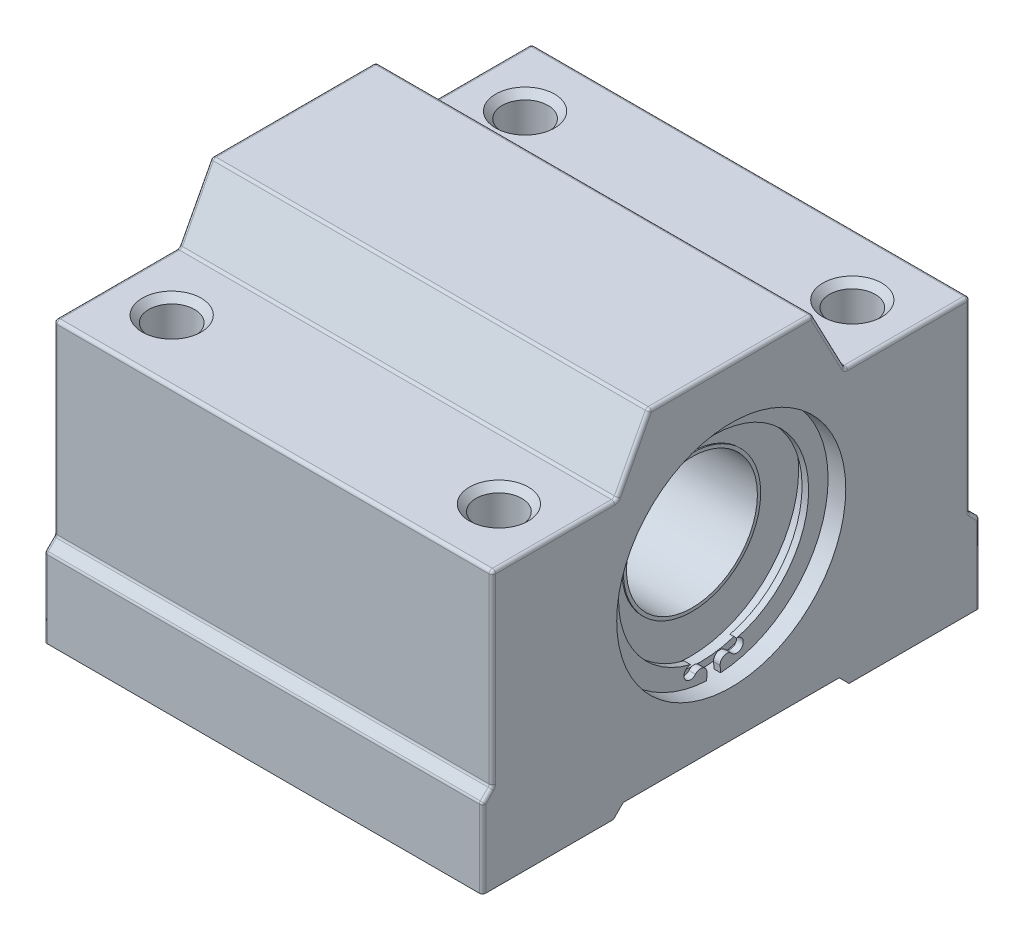
SolidWorks part; units mm, degrees
ref_plane "Front Plane" through (0, 0, 0) normal (0, 0, 1) x (1, 0, 0)
ref_plane "Top Plane" through (0, 0, 0) normal (0, 1, 0) x (1, 0, 0)
ref_plane "Right Plane" through (0, 0, 0) normal (1, 0, 0) x (0, 0, -1)
sketch "Sketch1" plane through (0, 0, 0) normal (1, 0, 0) x (0, 0, -1)
  line L1 (-18, -26) -> (-16.5, -24.5)
  line L2 (-16.5, -24.5) -> (16.5, -24.5)
  line L3 (16.5, -24.5) -> (18, -26)
  line L4 (18, -26) -> (38, -26)
  line L6 (38, -14) -> (36.5, -12.5)
  line L8 (36.5, 16) -> (17.5, 16)
  line L9 (17.5, 16) -> (12.5, 25.5)
  line L10 (12.5, 25.5) -> (-12.5, 25.5)
  line L11 (-12.5, 25.5) -> (-17.5, 16)
  line L12 (-17.5, 16) -> (-36.5, 16)
  line L15 (-38, -14) -> (-38, -26)
  line L16 (0, -24.5) -> (0, 25.5) construction
  line L17 (-16.278, 0) -> (14.0247, 0) construction
  line L18 (-38, -26) -> (-18, -26)
  line L19 (38, -14) -> (38, -26)
  line L20 (-36.5, -12.5) -> (-36.5, 16)
  line L21 (36.5, -12.5) -> (36.5, 16)
  line L22 (-27, 16) -> (-27, -26) construction
  line L23 (-27, -26) -> (27, 16) construction
  line L24 (27, 16) -> (27, -26) construction
  line L25 (-38, -14) -> (-36.5, -12.5)
  line L26 (-17.5, 0) -> (17.5, 0) construction
  circle A0 centre (0, 0) radius 17.5
  circle A1 centre (0, 0) radius 16.5
  circle A2 centre (0, 0) radius 10
  point P18 (0, 25.5)
  point P23 (0, 0)
  dimension "D12" = 20
  dimension "D1" = 76
  dimension "D2" = 42
  dimension "D3" = 26
  dimension "D5" = 51.5
  dimension "D6" = 54
  dimension "D4" = 12
  dimension "D7" = 1.5
  dimension "D8" = 25
  dimension "D9" = 1.5
  dimension "D10" = 20
  dimension "D11" = 1
extrude "Boss-Extrude1" add sketch "Sketch1" along normal blind 67 contours L25 L15 L18 L1 L2 L3 L4 L19 L6 L21 L8 L9 L10 L11 L12 L20 A0 region at (0, -25.0819, 28)
extrude "Extrude-Thin1" add sketch "Sketch1<4>" along normal blind 60.5 from offset 0.5 separate body thin contours A2 thin type one direction wall 0.5
sketch "Sketch1<4>" plane through (0, 0, 0) normal (1, 0, 0) x (0, 0, -1) same geometry as "Sketch1"
extrude "Boss-Extrude2" add sketch "Sketch1<5>" along normal blind 60 from offset 0.8 contours A1 A2 region at (0, 0, 16.0333)
sketch "Sketch1<5>" plane through (0, 0, 0) normal (1, 0, 0) x (0, 0, -1) same geometry as "Sketch1"
extrude "Boss-Extrude3" add sketch "Sketch1<6>" along normal blind 62 from offset 0.3 contours A0 A1 region at (0, 0, 17.005)
sketch "Sketch1<6>" plane through (0, 0, 0) normal (1, 0, 0) x (0, 0, -1) same geometry as "Sketch1"
ref_plane "Plane1" through (62.3, 0, 0) normal (1, 0, 0) x (0, 0, -1)
sketch "Sketch3" plane through (62.3, 0, 0) normal (1, 0, 0) x (0, 0, -1)
  line L0 (0, 0) -> (0, -50000) construction
  line L1 (-1.0042, -16.4694) -> (-1.065, -17.4676)
  line L2 (1.0042, -16.4694) -> (1.065, -17.4676)
  circle A0 centre (0, 0) radius 17.5 construction
  arc A1 (1.065, -17.4676) -> (-1.065, -17.4676) centre (0, 0) ccw
  circle A2 centre (0, 0) radius 16.5 construction
  arc A3 (0, -16.5) -> (1.0042, -16.4694) centre (0, 0) ccw
  arc A4 (-1.0042, -16.4694) -> (-2.7658, -15.7353) centre (-2, -16.3783) ccw
  circle A5 centre (-2, -16.3783) radius 0.25
  arc A6 (-2.2479, -16.3462) -> (-1.7516, -16.4068) centre (0, 0) ccw
  arc A7 (-2.7658, -15.7353) -> (-3.5134, -14.0925) centre (-3.5317, -15.0923) cw
  arc A8 (2.7658, -15.7353) -> (3.5134, -14.0925) centre (3.5317, -15.0923) ccw
  circle A10 centre (2, -16.3783) radius 0.25
  arc A11 (1.0042, -16.4694) -> (2.7658, -15.7353) centre (2, -16.3783) cw
  arc A13 (3.5134, -14.0925) -> (-3.5134, -14.0925) centre (0, 0) ccw
  point P12 (-1.1793, -6.3921)
  dimension "D1" = 0.5
  dimension "D2" = 2
  dimension "D3" = 1
  dimension "D4" = 2
extrude "Boss-Extrude4" add sketch "Sketch3" along normal blind 1 from offset 1 contours A11 A8 A13 A7 A4 L1 A1 L2
fillet "Fillet1" radius 0.5 32 edges at (33.5, -12.5, -36.5) (33.5, -12.5, 36.5) (33.5, -14, 38) (33.5, -14, -38) (33.5, 16, -17.5) (33.5, 16, 17.5) (33.5, 25.5, 12.5) (33.5, 25.5, -12.5) (33.5, 16, -36.5) (33.5, 16, 36.5) (67, 20.75, -15) (67, 20.75, 15) (67, 1.75, 36.5) (0, -13.25, 37.25) (0, 20.75, 15) (67, -13.25, -37.25) (67, -20, -38) (67, 1.75, -36.5) (67, 25.5, 0) (67, 16, -27) (67, 16, 27) (67, -13.25, 37.25) (67, -20, 38) (0, -20, -38) (0, -13.25, -37.25) (0, 1.75, -36.5) (0, 20.75, -15) (0, 16, -27) (0, 25.5, 0) (0, -20, 38) (0, 1.75, 36.5) (0, 16, 27)
sketch "Sketch4" plane through (0, -26, 0) normal (0, -1, 0) x (1, 0, 0)
  line L0 (33.5, 38) -> (33.5, -38) construction
  line L1 (66.5, 38) -> (0.5, 38) construction
  line L2 (66.5, -38) -> (0.5, -38) construction
  line L4 (-4.9444, 27) -> (27.0918, 27) construction
  line L6 (0, 0) -> (36.1646, 0) construction
  circle A0 centre (8.5, 27) radius 3.5
  circle A1 centre (58.5, 27) radius 3.5
  circle A2 centre (58.5, -27) radius 3.5
  circle A3 centre (8.5, -27) radius 3.5
  dimension "D2" = 7
  dimension "D1" = 27
  dimension "D3" = 50
extrude "Cut-Extrude3" cut sketch "Sketch4" against normal through all
chamfer "Chamfer1" distance 1 angle 45 6 edges at (58.5, 16, -30.5) (8.5, 16, -30.5) (8.5, 16, 23.5) (58.5, 16, 23.5) (58.5, -26, 30.5) (8.5, -26, 23.5)
equation "\"D1@Boss-Extrude2\"= \"D1@Boss-Extrude1\" - 2 - 5"
equation "\"D1@Boss-Extrude3\"= \"D1@Boss-Extrude1\" - 5"
equation "\"D1@Sketch4\"= \"D6@Sketch1\" / 2"
equation "\"D1@Extrude-Thin1\"= \"D1@Boss-Extrude3\" - 1.5"
